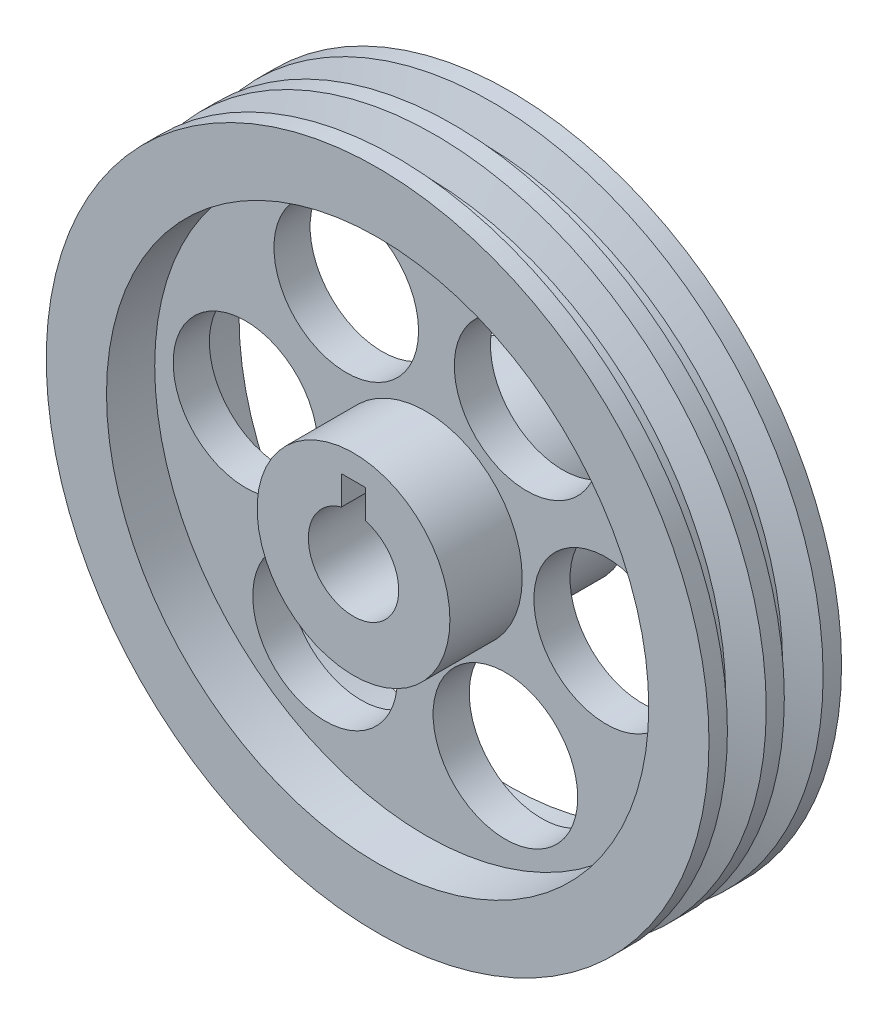
SolidWorks part; units mm, degrees
ref_plane "前视基准面" through (0, 0, 0) normal (0, 0, 1) x (1, 0, 0)
ref_plane "上视基准面" through (0, 0, 0) normal (0, 1, 0) x (1, 0, 0)
ref_plane "右视基准面" through (0, 0, 0) normal (1, 0, 0) x (0, 0, -1)
other "Configuration Table"
sketch "草图1" plane through (0, 0, 0) normal (0, 0, 1) x (1, 0, 0)
  line L0 (0, 0) -> (0, 7.5) construction
  line L1 (0, 12.0229) -> (2, 12.0229)
  line L2 (0, 12.0229) -> (-2, 12.0229)
  line L3 (-2, 12.0229) -> (-2, 7.2284)
  line L4 (2, 12.0229) -> (2, 7.2284)
  arc A0 (-2, 7.2284) -> (2, 7.2284) centre (0, 0) ccw
  circle A1 centre (0, 0) radius 30 construction
  circle A2 centre (0, 0) radius 16
  circle A3 centre (16.7238, 24.9061) radius 12
  circle A4 centre (29.9312, -2.0301) radius 12
  circle A5 centre (13.2075, -26.9363) radius 12
  circle A6 centre (-16.7238, -24.9061) radius 12
  circle A7 centre (-29.9312, 2.0301) radius 12
  circle A8 centre (-13.2075, 26.9363) radius 12
  circle A9 centre (0, 0) radius 45
  circle A10 centre (0, 0) radius 55
  dimension "D1" = 32
  dimension "D2" = 60
  dimension "D3" = 15
  dimension "D6" = 24
  dimension "D8" = 90
  dimension "D9" = 110
  dimension "D4" = 2
  dimension "D5" = 2
  dimension "D7" = 6
extrude "凸台-拉伸1" add sketch "草图1" along normal mid plane 30 contours A2 A0 L3 L2 L1 L4 region at (-15.5475, 0, 0)
extrude "凸台-拉伸2" add sketch "草图1<3>" along normal mid plane 6 contours A9 A2 A3 A4 A5 A6 A7 A8 region at (-43.7272, 0, 0)
sketch "草图1<3>" plane through (0, 0, 0) normal (0, 0, 1) x (1, 0, 0) same geometry as "草图1"
extrude "凸台-拉伸3" add sketch "草图1<4>" along normal mid plane 22 contours A10 A9 region at (-53.4444, 0, 0)
sketch "草图1<4>" plane through (0, 0, 0) normal (0, 0, 1) x (1, 0, 0) same geometry as "草图1"
ref_plane "基准面3" through (0, 0, 0) normal (1, 0, 0) x (0, 0, -1)
sketch "草图2" plane through (0, 0, 0) normal (1, 0, 0) x (0, 0, -1)
  line L1 (11, 55) -> (-11, 55) construction
  line L2 (-7.9433, 55) -> (-6.2216, 50)
  line L3 (-6.2216, 50) -> (-3.2216, 50)
  line L4 (-1.5, 55) -> (-3.2216, 50)
  line L5 (-1.5, 55) -> (1.5, 55)
  line L6 (0, 55) -> (0, 46.9157) construction
  line L8 (1.5, 55) -> (3.2216, 50)
  line L9 (6.2216, 50) -> (3.2216, 50)
  line L11 (11, -55) -> (11, 55) construction
  line L12 (7.9433, 55) -> (6.2216, 50)
  line L17 (-17.5037, 0) -> (32.3565, 0) construction
  line L18 (-7.9433, 55) -> (-1.5, 55)
  line L19 (1.5, 55) -> (7.9433, 55)
  line L20 (-7.9433, 55) -> (-1.5, 55)
  line L21 (1.5, 55) -> (7.9433, 55)
  point P18 (0, 55)
  dimension "D1" = 38
  dimension "D2" = 11
  dimension "D3" = 3
revolve "切除-旋转2" cut sketch "草图2" angle 360 about L17 region at (0, 52.8039, 4.7216) region at (0, 52.8039, -4.7216)
